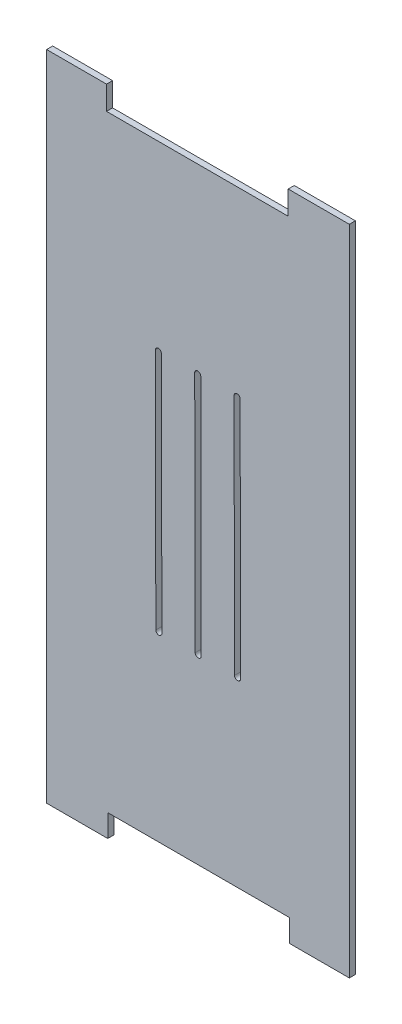
SolidWorks part; units mm, degrees
material "PET"
ref_plane "Front Plane" through (0, 0, 0) normal (0, 0, 1) x (1, 0, 0)
ref_plane "Top Plane" through (0, 0, 0) normal (0, 1, 0) x (1, 0, 0)
ref_plane "Right Plane" through (0, 0, 0) normal (1, 0, 0) x (0, 0, -1)
sketch "Sketch1" plane through (0, 0, 0) normal (0, 0, 1) x (1, 0, 0)
  line L1 (0, 0) -> (540, 0)
  line L2 (0, 0) -> (0, 540)
  line L3 (0, 540) -> (540, 540)
  line L4 (540, 0) -> (540, 540)
  dimension "D1" = 540
  dimension "D2" = 540
extrude "Boss-Extrude1" add sketch "Sketch1" along normal blind 5
sketch "Sketch2" plane through (0, 0, 5) normal (0, 0, 1) x (1, 0, 0)
  line L1 (0, 540) -> (20, 540)
  line L2 (0, 540) -> (0, 520)
  line L3 (0, 520) -> (20, 520)
  line L4 (20, 540) -> (20, 520)
  line L5 (540, 540) -> (520, 540)
  line L6 (540, 540) -> (540, 520)
  line L7 (540, 520) -> (520, 520)
  line L8 (520, 540) -> (520, 520)
  line L9 (540, 0) -> (520, 0)
  line L10 (540, 0) -> (540, 20)
  line L11 (540, 20) -> (520, 20)
  line L12 (520, 0) -> (520, 20)
  line L13 (0, 0) -> (20, 0)
  line L14 (0, 0) -> (0, 20)
  line L15 (0, 20) -> (20, 20)
  line L16 (20, 0) -> (20, 20)
  dimension "D1" = 20
  dimension "D2" = 20
  dimension "D3" = 20
  dimension "D4" = 20
  dimension "D5" = 20
  dimension "D6" = 20
  dimension "D7" = 20
  dimension "D8" = 20
extrude "Cut-Extrude1" [suppressed] cut sketch "Sketch2" against normal blind 5
chamfer "Chamfer1" [suppressed] distance 2 angle 45
chamfer "Chamfer2" distance 0.5 angle 45 8 edges at (270, 0, 0) (540, 270, 0) (270, 540, 0) (0, 270, 0) (270, 540, 5) (540, 270, 5) (270, 0, 5) (0, 270, 5)
chamfer "Chamfer3" distance 2 angle 45 4 edges at (0, 540, 2.5) (540, 540, 2.5) (540, 0, 2.5) (0, 0, 2.5)
sketch "Sketch3" plane through (0, 0, 5) normal (0, 0, 1) x (1, 0, 0)
  line L5 (2, 540) -> (538, 540) construction
  line L6 (195, 540) -> (345, 540)
  line L7 (195, 540) -> (195, 520)
  line L8 (195, 520) -> (345, 520)
  line L9 (345, 540) -> (345, 520)
  line L10 (270, 0.5) -> (270, 304.9042) construction
  line L11 (1.5, 0.5) -> (538.5, 0.5) construction
  dimension "D1" = 150
  dimension "D2" = 20
  dimension "D3" = 75
extrude "Cut-Extrude2" cut sketch "Sketch3" against normal blind 10
sketch "Sketch4" plane through (0, 0, 5) normal (0, 0, 1) x (1, 0, 0)
  line L0 (1.5, 0.5) -> (539.5, 538.5)
  point P4 (270.5, 269.5)
ref_axis "Axis1" through (270.5, 269.5, 5) along (0, 0, 1)
pattern_circular "CirPattern1" count 4 over 360 about axis through (270.5, 269.5, 5) along (0, 0, 1) of "Cut-Extrude2"
sketch "Sketch6" plane through (0, 0, 5) normal (0, 0, 1) x (1, 0, 0)
  line L0 (270, 520) -> (271, 19) construction
  line L1 (195, 520) -> (345, 520) construction
  line L2 (346, 19) -> (196, 19) construction
  line L3 (20, 269) -> (521, 270) construction
  line L4 (20, 194) -> (20, 344) construction
  line L5 (521, 345) -> (521, 195) construction
  line L6 (270.3004, 369.5) -> (270.6996, 169.5) construction
  line L7 (272.8004, 369.505) -> (273.1996, 169.505)
  line L8 (267.8004, 369.495) -> (268.1996, 169.495)
  arc A0 (272.8004, 369.505) -> (267.8004, 369.495) centre (270.3004, 369.5) ccw
  arc A1 (268.1996, 169.495) -> (273.1996, 169.505) centre (270.6996, 169.5) ccw
  point P14 (270.5, 269.5)
  point P19 (270.5, 269.5)
  dimension "D1" = 2.5
  dimension "D2" = 200
extrude "Cut-Extrude3" cut sketch "Sketch6" against normal blind 10 contours L7 A1 L8 A0
pattern_linear "LPattern1" count 2 spacing 32.5 along (1, 0, 0) of "Cut-Extrude3"
pattern_linear "LPattern2" count 2 spacing 32.5 along (-1, 0, 0) of "Cut-Extrude3"
sketch "Sketch7" plane through (0, 0, 5) normal (0, 0, 1) x (1, 0, 0)
  line L0 (195, 539.5) -> (1.5, 539.5) construction
  line L1 (145.5, 539.5) -> (395.5, 539.5)
  line L2 (145.5, 539.5) -> (145.5, 0.5)
  line L3 (145.5, 0.5) -> (395.5, 0.5)
  line L4 (395.5, 539.5) -> (395.5, 0.5)
  line L5 (346, 0.5) -> (538.5, 0.5) construction
  line L7 (-83.8131, 621.7989) -> (613.454, 621.7989)
  line L8 (-83.8131, 621.7989) -> (-83.8131, -87.9752)
  line L9 (-83.8131, -87.9752) -> (613.454, -87.9752)
  line L10 (613.454, 621.7989) -> (613.454, -87.9752)
  dimension "D1" = 250
  dimension "D2" = 125
extrude "Cut-Extrude4" cut sketch "Sketch7" against normal through all
